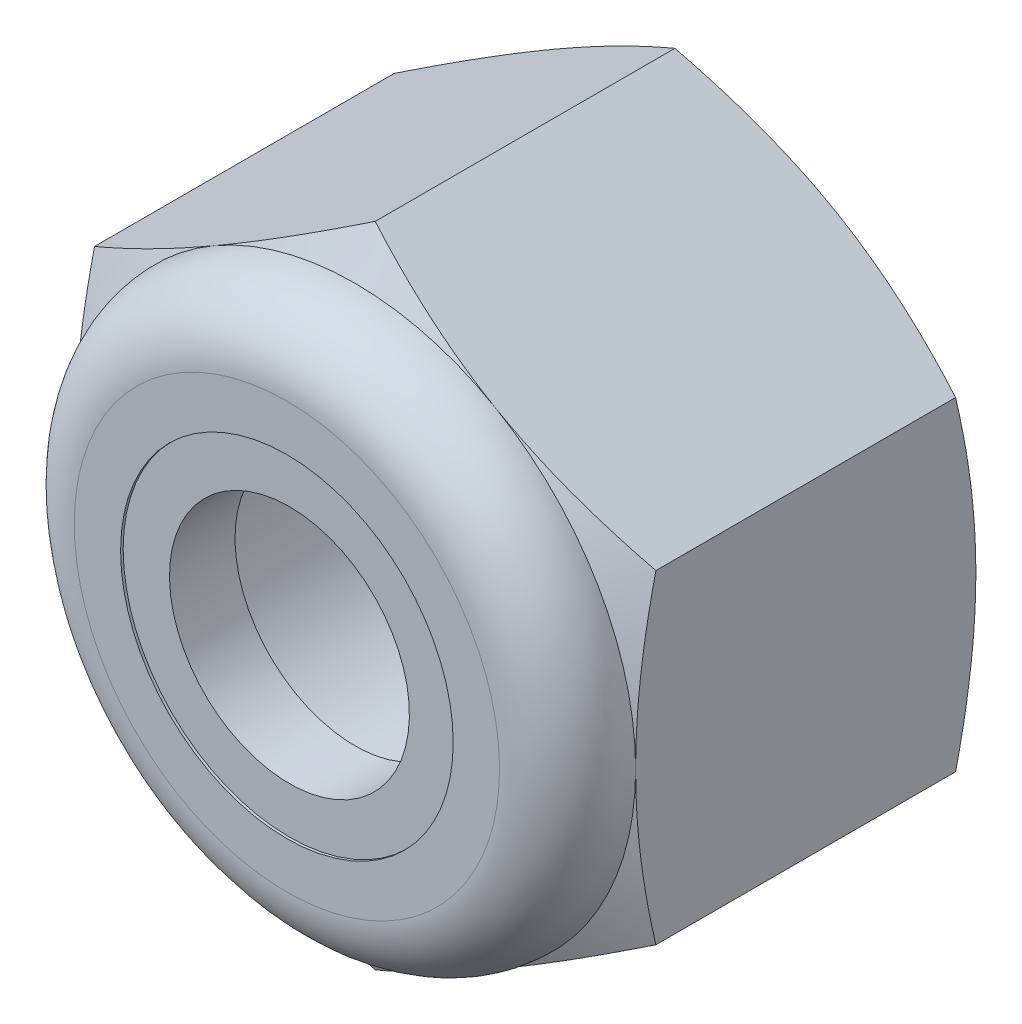
SolidWorks part; units mm, degrees
material "Alloy Steel"
ref_plane "Front Plane" through (0, 0, 0) normal (0, 0, 1) x (1, 0, 0)
ref_plane "Top Plane" through (0, 0, 0) normal (0, 1, 0) x (1, 0, 0)
ref_plane "Right Plane" through (0, 0, 0) normal (1, 0, 0) x (0, 0, -1)
sketch "Sketch1" plane through (0, 0, 0) normal (0, 0, 1) x (1, 0, 0)
  line L1 (0, 3.1754) -> (-2.75, 1.5877)
  line L2 (-2.75, 1.5877) -> (-2.75, -1.5877)
  line L3 (-2.75, -1.5877) -> (0, -3.1754)
  line L4 (0, -3.1754) -> (2.75, -1.5877)
  line L5 (2.75, -1.5877) -> (2.75, 1.5877)
  line L6 (2.75, 1.5877) -> (0, 3.1754)
  circle A0 centre (0, 0) radius 2.75 construction
  circle A1 centre (0, 0) radius 1.5
  point P10 (0, -1.5)
  point P11 (0, 1.5)
  point P12 (0, 2.75)
  dimension "Thread Size" = 3
  dimension "Width" = 5.5
sketch "Sketch2" plane through (0, 0, 0) normal (1, 0, 0) x (0, 0, -1)
  line L0 (2, 0) -> (-2, 0) construction
  line L1 (-2, 1.5) -> (2, 1.5) construction
  line L2 (-1.975, -1.6293) -> (-3.27, -1.6293) construction
  line L3 (-2.4688, 1.5541) -> (-1.9688, 1.5541) construction
  line L4 (-1.9688, 1.5541) -> (-2.2188, 1.1211) construction
  line L5 (-2.2188, 1.1211) -> (-2.4688, 1.5541) construction
  line L6 (-2.4375, 1.5) -> (-2, 1.5) construction
  line L7 (-2.25, 1.1752) -> (-2.1875, 1.1752) construction
  line L8 (-2.2188, 1.1752) -> (-2.2188, 1.1211) construction
  line L9 (-2.2188, 1.5) -> (-2.2188, 1.5541) construction
  line L10 (-1.9844, 1.5271) -> (-2.4531, 1.5271)
  line L11 (-2.4531, 1.5271) -> (-2.25, 1.1752)
  line L12 (-2.25, 1.1752) -> (-2.1875, 1.1752)
  line L13 (-2.1875, 1.1752) -> (-1.9844, 1.5271)
  line L14 (2, 0) -> (3.27, 0)
  line L15 (3.27, 0) -> (3.27, 4.4454)
  line L16 (0, 4.4454) -> (0, 3.1754) construction
  line L17 (0, 3.1754) -> (0, 1.5877) construction
  line L18 (2, 2.75) -> (-1.3333, 2.75) construction
  line L19 (-2.25, -1.1752) -> (-2.1875, -1.1752) construction
  line L20 (2, 2.75) -> (2, 0)
  line L21 (1.8016, 3.1754) -> (-1.135, 3.1754)
  line L22 (2, 2.75) -> (1.8016, 3.1754)
  line L23 (-2, 0) -> (-2, 2.0833) construction
  line L24 (-1.3333, 2.75) -> (-1.135, 3.1754)
  line L25 (3.27, 4.4454) -> (-3.27, 4.4454)
  line L26 (-2, 2.0833) -> (-3.27, 2.0833)
  line L27 (-3.27, 2.0833) -> (-3.27, 4.4454)
  line L28 (-1.975, 2.0833) -> (-1.975, 1.1752) construction
  line L29 (-1.975, 1.6293) -> (-3.27, 1.6293)
  line L30 (-3.27, 1.6293) -> (-3.27, 0)
  line L31 (-3.27, 0) -> (-1.3333, 0)
  line L32 (-1.3333, 0) -> (-1.3333, 2.725)
  line L33 (-1.975, 1.6293) -> (-1.975, 2.0833)
  arc A0 (-1.3333, 2.75) -> (-2, 2.0833) centre (-1.3333, 2.0833) ccw
  arc A1 (-1.3333, 2.725) -> (-1.975, 2.0833) centre (-1.3333, 2.0833) ccw
  point P4 (0, 0)
  point P18 (-2.2188, 1.5271)
  point P22 (-2.2188, 1.5271)
  point P33 (0, 3.1754)
  point P48 (-3.27, -1.6293)
  point P51 (-2.25, -1.1752)
  dimension "Height" = 4
  dimension "Pitch" = 0.5
  dimension "D1" = 0.0625
  dimension "D2" = 1.27
  dimension "D3" = 25
  dimension "D4" = 0.6667
  dimension "D5" = 25
  dimension "D6" = 0.025
sketch "Sketch3" plane through (0, 0, 0) normal (0, 0, 1) x (1, 0, 0)
  line L0 (0, -3.1754) -> (2.75, -1.5877) construction
  line L1 (2.75, -1.5877) -> (2.75, 1.5877) construction
  line L2 (2.75, 1.5877) -> (0, 3.1754) construction
  line L3 (0, 3.1754) -> (-2.75, 1.5877) construction
  line L4 (-2.75, 1.5877) -> (-2.75, -1.5877) construction
  line L5 (-2.75, -1.5877) -> (0, -3.1754) construction
  line L6 (0, -3.1754) -> (2.75, -1.5877)
  line L7 (2.75, -1.5877) -> (2.75, 1.5877)
  line L8 (2.75, 1.5877) -> (0, 3.1754)
  line L9 (0, 3.1754) -> (-2.75, 1.5877)
  line L10 (-2.75, 1.5877) -> (-2.75, -1.5877)
  line L11 (-2.75, -1.5877) -> (0, -3.1754)
  circle A0 centre (0, 0) radius 1.5 construction
  circle A1 centre (0, 0) radius 1.5
extrude "Boss-Extrude1" add sketch "Sketch3" along normal mid plane 4
sketch "Sketch4" plane through (0, 0, 0) normal (1, 0, 0) x (0, 0, -1)
  line L0 (3.27, 4.4454) -> (-3.27, 4.4454) construction
  line L1 (-3.27, 2.0833) -> (-3.27, 4.4454) construction
  line L2 (-2, 2.0833) -> (-3.27, 2.0833) construction
  line L3 (-1.3333, 2.75) -> (-1.135, 3.1754) construction
  line L4 (1.8016, 3.1754) -> (-1.135, 3.1754) construction
  line L5 (2, 2.75) -> (1.8016, 3.1754) construction
  line L6 (2, 2.75) -> (2, 0) construction
  line L7 (2, 0) -> (3.27, 0) construction
  line L8 (3.27, 0) -> (3.27, 4.4454) construction
  line L9 (-3.27, 1.6293) -> (-3.27, 0) construction
  line L10 (-3.27, 0) -> (-1.3333, 0) construction
  line L11 (-1.3333, 0) -> (-1.3333, 2.725) construction
  line L12 (-1.975, 1.6293) -> (-1.975, 2.0833) construction
  line L13 (-1.975, 1.6293) -> (-3.27, 1.6293) construction
  line L14 (3.27, 4.4454) -> (-3.27, 4.4454)
  line L15 (-3.27, 2.0833) -> (-3.27, 4.4454)
  line L16 (-2, 2.0833) -> (-3.27, 2.0833)
  line L17 (-1.3333, 2.75) -> (-1.135, 3.1754)
  line L18 (1.8016, 3.1754) -> (-1.135, 3.1754)
  line L19 (2, 2.75) -> (1.8016, 3.1754)
  line L20 (2, 2.75) -> (2, 0)
  line L21 (2, 0) -> (3.27, 0)
  line L22 (3.27, 0) -> (3.27, 4.4454)
  line L23 (-3.27, 1.6293) -> (-3.27, 0)
  line L24 (-3.27, 0) -> (-1.3333, 0)
  line L25 (-1.3333, 0) -> (-1.3333, 2.725)
  line L26 (-1.975, 1.6293) -> (-1.975, 2.0833)
  line L27 (-1.975, 1.6293) -> (-3.27, 1.6293)
  arc A0 (-1.3333, 2.75) -> (-2, 2.0833) centre (-1.3333, 2.0833) ccw construction
  arc A1 (-1.3333, 2.725) -> (-1.975, 2.0833) centre (-1.3333, 2.0833) ccw construction
  arc A2 (-1.3333, 2.75) -> (-2, 2.0833) centre (-1.3333, 2.0833) ccw
  arc A3 (-1.3333, 2.725) -> (-1.975, 2.0833) centre (-1.3333, 2.0833) ccw
revolve "Cut-Revolve1" cut sketch "Sketch4" angle 360 about L0
sketch "Sketch5" plane through (0, 0, 0) normal (1, 0, 0) x (0, 0, -1)
  line L0 (-1.975, 2.0833) -> (-1.975, 1.1752) construction
  line L1 (-1.3333, 0) -> (-1.3333, 2.725) construction
  line L2 (-1.975, 2.0833) -> (-1.975, 1.1752)
  line L3 (-1.3333, 1.1752) -> (-1.3333, 2.725)
  line L4 (-1.975, 1.1752) -> (-1.3333, 1.1752)
  arc A0 (-1.3333, 2.725) -> (-1.975, 2.0833) centre (-1.3333, 2.0833) ccw construction
  arc A1 (-1.3333, 2.725) -> (-1.975, 2.0833) centre (-1.3333, 2.0833) ccw
revolve "Revolve1" add sketch "Sketch5" angle 360 about L0
sketch "Sketch6" [suppressed] plane through (0, 0, 2) normal (0, 0, 1) x (1, 0, 0)
  circle A0 centre (0, 0) radius 1.5 construction
  circle A1 centre (0, 0) radius 1.5
curve "Helix/Spiral1" [suppressed] pitch 0.5 height 4.5 turns 9
sketch "Sketch7" [suppressed] plane through (0, 0, 0) normal (1, 0, 0) x (0, 0, -1)
  line L0 (-2.4531, 1.5271) -> (-2.25, 1.1752) construction
  line L1 (-2.25, 1.1752) -> (-2.1875, 1.1752) construction
  line L2 (-2.1875, 1.1752) -> (-1.9844, 1.5271) construction
  line L3 (-1.9844, 1.5271) -> (-2.4531, 1.5271) construction
  line L4 (-2.4531, 1.5271) -> (-2.25, 1.1752)
  line L5 (-2.25, 1.1752) -> (-2.1875, 1.1752)
  line L6 (-2.1875, 1.1752) -> (-1.9844, 1.5271)
  line L7 (-1.9844, 1.5271) -> (-2.4531, 1.5271)
sweep "Sweep1" [suppressed] add profiles "Sketch7" path "Helix/Spiral1"
sketch "Sketch8" [suppressed] plane through (0, 0, -2) normal (0, 0, -1) x (-1, 0, 0)
  circle A2 centre (0, 0) radius 1.5271
  point P2 (0, 1.5271)
extrude "Cut-Extrude1" [suppressed] cut sketch "Sketch8" along normal through all and the other way through all draft 60
sketch "Sketch9" [suppressed] plane through (0, 0, 1.3333) normal (0, 0, 1) x (1, 0, 0)
  circle A2 centre (0, 0) radius 1.5271
  circle A3 centre (0, 0) radius 1.1752 construction
  point P2 (0, 1.5271)
  point P4 (0, 1.1752)
extrude "Cut-Extrude2" [suppressed] cut sketch "Sketch9" along normal through all and the other way through all draft 60
equation "\"D1@Sketch2\" = \"Pitch@Sketch2\" / 8"
equation "\"D4@Sketch2\"=\"Height@Sketch2\"/6"
equation "\"D1@Boss-Extrude1\"=\"Height@Sketch2\""
equation "\"D3@Helix/Spiral1\"=\"Height@Sketch2\"+\"Pitch@Sketch2\""
equation "\"D4@Helix/Spiral1\"=\"Pitch@Sketch2\""
equation "\"D6@Sketch2\"=\"Pitch@Sketch2\"*0.05"
